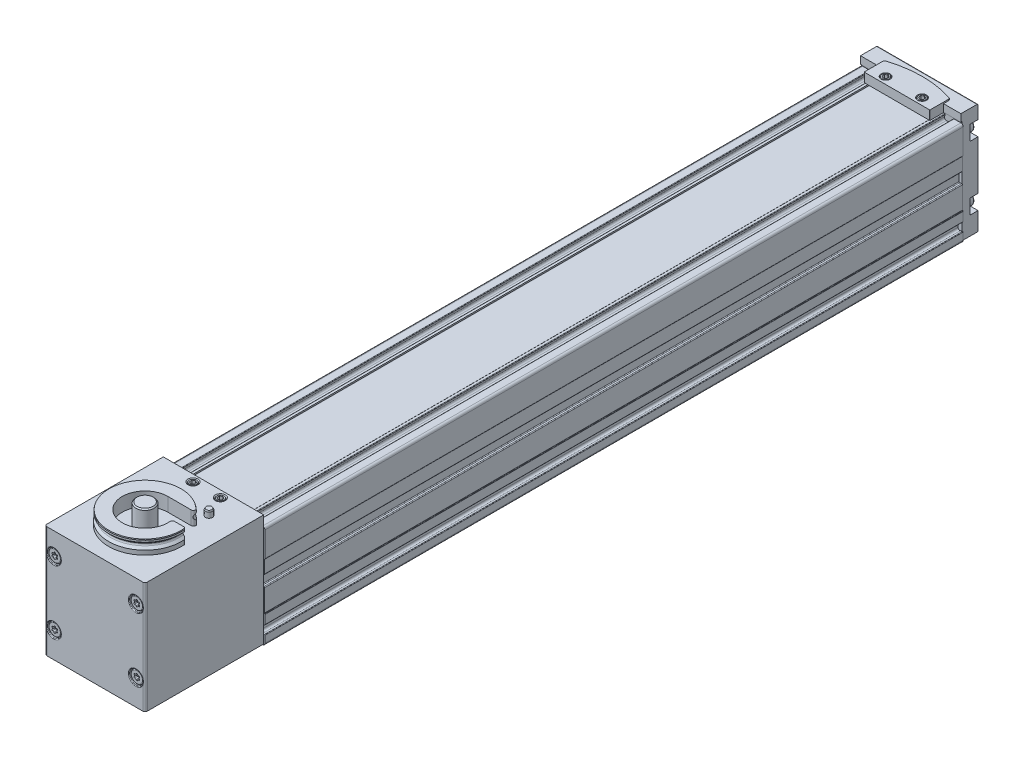
SolidWorks part; units mm, degrees
ref_plane "Front Plane" through (0, 0, 0) normal (0, 0, 1) x (1, 0, 0)
ref_plane "Top Plane" through (0, 0, 0) normal (0, 1, 0) x (1, 0, 0)
ref_plane "Right Plane" through (0, 0, 0) normal (1, 0, 0) x (0, 0, -1)
sketch "Sketch1" plane through (0, 0, 0) normal (0, 1, 0) x (1, 0, 0)
  line L0 (-21, -52) -> (21, -52)
  line L1 (22, -51) -> (22, 0)
  line L2 (22, 0) -> (-22, 0)
  line L3 (-22, 0) -> (-22, -51)
  arc A0 (-22, -51) -> (-21, -52) centre (-21, -51) ccw
  arc A1 (21, -52) -> (22, -51) centre (21, -51) ccw
extrude "Boss-Extrude1" add sketch "Sketch1" along normal blind 49
sketch "Sketch2" plane through (0, 0, 0) normal (0, 0, 1) x (1, 0, 0)
  line L0 (-22.5, -0.5) -> (22.5, -0.5)
  line L1 (22.5, -0.5) -> (22.5, 44.5)
  line L2 (22.5, 44.5) -> (13.4, 44.5)
  line L3 (13.4, 44.5) -> (13.4, 43.9)
  line L4 (13.4, 43.9) -> (-13.4, 43.9)
  line L5 (-13.4, 43.9) -> (-13.4, 44.5)
  line L6 (-13.4, 44.5) -> (-22.5, 44.5)
  line L7 (-22.5, 44.5) -> (-22.5, -0.5)
extrude "Boss-Extrude2" add sketch "Sketch2" against normal blind 306
sketch "Sketch3" plane through (0, 0, 0) normal (0, 0, 1) x (1, 0, 0)
  line L0 (-32.5, -5.5) -> (32.5, -5.5)
  line L1 (32.5, -5.5) -> (32.5, 49.5)
  line L2 (32.5, 49.5) -> (-32.5, 49.5)
  line L3 (-32.5, 49.5) -> (-32.5, -5.5)
  line L4 (-21.5, -0.5) -> (-18.4606, -0.5)
  line L5 (-18.2675, -0.2482) -> (-18.5464, 0.7929)
  line L6 (-17.7737, 1.8) -> (-15.1263, 1.8)
  line L7 (-14.3536, 0.7929) -> (-14.6325, -0.2482)
  line L8 (-14.4394, -0.5) -> (-7.5828, -0.5)
  line L9 (-7.4414, -0.4414) -> (-7.3086, -0.3086)
  line L10 (-7.1672, -0.25) -> (-4.8328, -0.25)
  line L11 (-4.6914, -0.3086) -> (-4.5586, -0.4414)
  line L12 (-4.4172, -0.5) -> (4.4172, -0.5)
  line L13 (4.5586, -0.4414) -> (4.6914, -0.3086)
  line L14 (4.8328, -0.25) -> (7.1672, -0.25)
  line L15 (7.3086, -0.3086) -> (7.4414, -0.4414)
  line L16 (7.5828, -0.5) -> (14.4394, -0.5)
  line L17 (14.6325, -0.2482) -> (14.3536, 0.7929)
  line L18 (15.1263, 1.8) -> (17.7737, 1.8)
  line L19 (18.5464, 0.7929) -> (18.2675, -0.2482)
  line L20 (18.4606, -0.5) -> (21.5, -0.5)
  line L21 (22.5, 0.5) -> (22.5, 3.5394)
  line L22 (22.2482, 3.7325) -> (21.2071, 3.4536)
  line L23 (20.2, 4.2263) -> (20.2, 6.8737)
  line L24 (21.2071, 7.6464) -> (22.2482, 7.3675)
  line L25 (22.5, 7.5606) -> (22.5, 11.4172)
  line L26 (22.4414, 11.5586) -> (22.3086, 11.6914)
  line L27 (22.25, 11.8328) -> (22.25, 21.3925)
  line L28 (21.8979, 21.6879) -> (21.0021, 21.53)
  line L29 (20.65, 21.8254) -> (20.65, 26.1746)
  line L30 (21.0021, 26.47) -> (21.8979, 26.3121)
  line L31 (22.25, 26.6075) -> (22.25, 32.1672)
  line L32 (22.3086, 32.3086) -> (22.4414, 32.4414)
  line L33 (22.5, 32.5828) -> (22.5, 43.5)
  line L34 (21.5, 44.5) -> (18.4606, 44.5)
  line L35 (18.2675, 44.2482) -> (18.5464, 43.2071)
  line L36 (17.7737, 42.2) -> (15.1263, 42.2)
  line L37 (14.3536, 43.2071) -> (14.6325, 44.2482)
  line L38 (14.4394, 44.5) -> (-14.4394, 44.5)
  line L39 (-14.6325, 44.2482) -> (-14.3536, 43.2071)
  line L40 (-15.1263, 42.2) -> (-17.7737, 42.2)
  line L41 (-18.5464, 43.2071) -> (-18.2675, 44.2482)
  line L42 (-18.4606, 44.5) -> (-21.5, 44.5)
  line L43 (-22.5, 43.5) -> (-22.5, 32.5828)
  line L44 (-22.4414, 32.4414) -> (-22.3086, 32.3086)
  line L45 (-22.25, 32.1672) -> (-22.25, 26.6075)
  line L46 (-21.8979, 26.3121) -> (-21.0021, 26.47)
  line L47 (-20.65, 26.1746) -> (-20.65, 21.8254)
  line L48 (-21.0021, 21.53) -> (-21.8979, 21.6879)
  line L49 (-22.25, 21.3925) -> (-22.25, 11.8328)
  line L50 (-22.3086, 11.6914) -> (-22.4414, 11.5586)
  line L51 (-22.5, 11.4172) -> (-22.5, 7.5606)
  line L52 (-22.2482, 7.3675) -> (-21.2071, 7.6464)
  line L53 (-20.2, 6.8737) -> (-20.2, 4.2263)
  line L54 (-21.2071, 3.4536) -> (-22.2482, 3.7325)
  line L55 (-22.5, 3.5394) -> (-22.5, 0.5)
  arc A0 (-22.5, 0.5) -> (-21.5, -0.5) centre (-21.5, 0.5) ccw
  arc A1 (-18.4606, -0.5) -> (-18.2675, -0.2482) centre (-18.4606, -0.3) ccw
  arc A2 (-18.5464, 0.7929) -> (-17.7737, 1.8) centre (-17.7737, 1) cw
  arc A3 (-15.1263, 1.8) -> (-14.3536, 0.7929) centre (-15.1263, 1) cw
  arc A4 (-14.6325, -0.2482) -> (-14.4394, -0.5) centre (-14.4394, -0.3) ccw
  arc A5 (-7.5828, -0.5) -> (-7.4414, -0.4414) centre (-7.5828, -0.3) ccw
  arc A6 (-7.3086, -0.3086) -> (-7.1672, -0.25) centre (-7.1672, -0.45) cw
  arc A7 (-4.8328, -0.25) -> (-4.6914, -0.3086) centre (-4.8328, -0.45) cw
  arc A8 (-4.5586, -0.4414) -> (-4.4172, -0.5) centre (-4.4172, -0.3) ccw
  arc A9 (4.4172, -0.5) -> (4.5586, -0.4414) centre (4.4172, -0.3) ccw
  arc A10 (4.6914, -0.3086) -> (4.8328, -0.25) centre (4.8328, -0.45) cw
  arc A11 (7.1672, -0.25) -> (7.3086, -0.3086) centre (7.1672, -0.45) cw
  arc A12 (7.4414, -0.4414) -> (7.5828, -0.5) centre (7.5828, -0.3) ccw
  arc A13 (14.4394, -0.5) -> (14.6325, -0.2482) centre (14.4394, -0.3) ccw
  arc A14 (14.3536, 0.7929) -> (15.1263, 1.8) centre (15.1263, 1) cw
  arc A15 (17.7737, 1.8) -> (18.5464, 0.7929) centre (17.7737, 1) cw
  arc A16 (18.2675, -0.2482) -> (18.4606, -0.5) centre (18.4606, -0.3) ccw
  arc A17 (21.5, -0.5) -> (22.5, 0.5) centre (21.5, 0.5) ccw
  arc A18 (22.5, 3.5394) -> (22.2482, 3.7325) centre (22.3, 3.5394) ccw
  arc A19 (21.2071, 3.4536) -> (20.2, 4.2263) centre (21, 4.2263) cw
  arc A20 (20.2, 6.8737) -> (21.2071, 7.6464) centre (21, 6.8737) cw
  arc A21 (22.2482, 7.3675) -> (22.5, 7.5606) centre (22.3, 7.5606) ccw
  arc A22 (22.5, 11.4172) -> (22.4414, 11.5586) centre (22.3, 11.4172) ccw
  arc A23 (22.3086, 11.6914) -> (22.25, 11.8328) centre (22.45, 11.8328) cw
  arc A24 (22.25, 21.3925) -> (21.8979, 21.6879) centre (21.95, 21.3925) ccw
  arc A25 (21.0021, 21.53) -> (20.65, 21.8254) centre (20.95, 21.8254) cw
  arc A26 (20.65, 26.1746) -> (21.0021, 26.47) centre (20.95, 26.1746) cw
  arc A27 (21.8979, 26.3121) -> (22.25, 26.6075) centre (21.95, 26.6075) ccw
  arc A28 (22.25, 32.1672) -> (22.3086, 32.3086) centre (22.45, 32.1672) cw
  arc A29 (22.4414, 32.4414) -> (22.5, 32.5828) centre (22.3, 32.5828) ccw
  arc A30 (22.5, 43.5) -> (21.5, 44.5) centre (21.5, 43.5) ccw
  arc A31 (18.4606, 44.5) -> (18.2675, 44.2482) centre (18.4606, 44.3) ccw
  arc A32 (18.5464, 43.2071) -> (17.7737, 42.2) centre (17.7737, 43) cw
  arc A33 (15.1263, 42.2) -> (14.3536, 43.2071) centre (15.1263, 43) cw
  arc A34 (14.6325, 44.2482) -> (14.4394, 44.5) centre (14.4394, 44.3) ccw
  arc A35 (-14.4394, 44.5) -> (-14.6325, 44.2482) centre (-14.4394, 44.3) ccw
  arc A36 (-14.3536, 43.2071) -> (-15.1263, 42.2) centre (-15.1263, 43) cw
  arc A37 (-17.7737, 42.2) -> (-18.5464, 43.2071) centre (-17.7737, 43) cw
  arc A38 (-18.2675, 44.2482) -> (-18.4606, 44.5) centre (-18.4606, 44.3) ccw
  arc A39 (-21.5, 44.5) -> (-22.5, 43.5) centre (-21.5, 43.5) ccw
  arc A40 (-22.5, 32.5828) -> (-22.4414, 32.4414) centre (-22.3, 32.5828) ccw
  arc A41 (-22.3086, 32.3086) -> (-22.25, 32.1672) centre (-22.45, 32.1672) cw
  arc A42 (-22.25, 26.6075) -> (-21.8979, 26.3121) centre (-21.95, 26.6075) ccw
  arc A43 (-21.0021, 26.47) -> (-20.65, 26.1746) centre (-20.95, 26.1746) cw
  arc A44 (-20.65, 21.8254) -> (-21.0021, 21.53) centre (-20.95, 21.8254) cw
  arc A45 (-21.8979, 21.6879) -> (-22.25, 21.3925) centre (-21.95, 21.3925) ccw
  arc A46 (-22.25, 11.8328) -> (-22.3086, 11.6914) centre (-22.45, 11.8328) cw
  arc A47 (-22.4414, 11.5586) -> (-22.5, 11.4172) centre (-22.3, 11.4172) ccw
  arc A48 (-22.5, 7.5606) -> (-22.2482, 7.3675) centre (-22.3, 7.5606) ccw
  arc A49 (-21.2071, 7.6464) -> (-20.2, 6.8737) centre (-21, 6.8737) cw
  arc A50 (-20.2, 4.2263) -> (-21.2071, 3.4536) centre (-21, 4.2263) cw
  arc A51 (-22.2482, 3.7325) -> (-22.5, 3.5394) centre (-22.3, 3.5394) ccw
extrude "Cut-Extrude1" cut sketch "Sketch3" against normal blind 306
ref_plane "Plane1" through (0, 0, -153) normal (0, 0, 1) x (1, 0, 0)
ref_plane "Plane2" through (0, 0, -271.25) normal (0, 0, 1) x (1, 0, 0)
sketch "Sketch4" plane through (0, 0, -271.25) normal (0, 0, 1) x (1, 0, 0)
  line L0 (-32.5, -5.5) -> (32.5, -5.5)
  line L1 (32.5, -5.5) -> (32.5, 49.5)
  line L2 (32.5, 49.5) -> (-32.5, 49.5)
  line L3 (-32.5, 49.5) -> (-32.5, -5.5)
  line L4 (-22.5, -0.5) -> (22.5, -0.5)
  line L5 (22.5, -0.5) -> (22.5, 44.5)
  line L6 (22.5, 44.5) -> (13.4, 44.5)
  line L7 (13.4, 44.5) -> (13.4, 43.9)
  line L8 (13.4, 43.9) -> (10, 43.9)
  line L9 (10, 43.9) -> (10, 28)
  line L10 (10, 28) -> (17, 28)
  line L11 (17, 28) -> (17, 21.5)
  line L12 (17, 21.5) -> (-17, 21.5)
  line L13 (-17, 21.5) -> (-17, 28)
  line L14 (-17, 28) -> (-10, 28)
  line L15 (-10, 28) -> (-10, 43.9)
  line L16 (-10, 43.9) -> (-13.4, 43.9)
  line L17 (-13.4, 43.9) -> (-13.4, 44.5)
  line L18 (-13.4, 44.5) -> (-22.5, 44.5)
  line L19 (-22.5, 44.5) -> (-22.5, -0.5)
extrude "Cut-Extrude2" cut sketch "Sketch4" along normal blind 266.5
sketch "Sketch5" plane through (0, 0, 0) normal (0, 0, 1) x (1, 0, 0)
  line L0 (-13, 44.06) -> (13, 44.06)
  line L1 (13, 44.06) -> (13, 44.16)
  line L2 (13, 44.16) -> (-13, 44.16)
  line L3 (-13, 44.16) -> (-13, 44.06)
extrude "Boss-Extrude3" add sketch "Sketch5" against normal blind 306
ref_plane "Plane3" through (0, 49, 0) normal (0, 1, 0) x (1, 0, 0)
sketch "Sketch6" plane through (0, 49, 0) normal (0, 1, 0) x (1, 0, 0)
  line L0 (14.9666, -28) -> (10.9545, -28)
  line L1 (0, -20) -> (10.198, -20)
  arc A0 (10.8779, -18.2667) -> (15.9644, -28.9333) centre (0, -30) ccw
  arc A1 (15.9644, -28.9333) -> (14.9666, -28) centre (14.9666, -29) ccw
  arc A2 (10.9545, -28) -> (9.9586, -29.0909) centre (10.9545, -29) ccw
  arc A3 (9.9586, -29.0909) -> (0, -20) centre (0, -30) cw
  arc A4 (10.198, -20) -> (10.8779, -18.2667) centre (10.198, -19) ccw
extrude "Boss-Extrude4" add sketch "Sketch6" along normal blind 6
sketch "Sketch7" plane through (0, 0, 0) normal (1, 0, 0) x (0, 0, -1)
  line L0 (-14.9737, 51.8697) -> (-14, 50.8959)
  line L1 (-14, 50.8959) -> (-14, 49)
  line L2 (-14, 49) -> (-4, 49)
  line L3 (-4, 49) -> (-4, 55)
  line L4 (-4, 55) -> (-14.2072, 55)
  line L5 (-14.2072, 55) -> (-14.1, 54.6)
  line L6 (-14.1, 54.6) -> (-14.1, 53.8041)
  line L7 (-14.1, 53.8041) -> (-14.9737, 52.9303)
  line L8 (-30, 49) -> (-30, 55) construction
  arc A0 (-14.9737, 52.9303) -> (-14.9737, 51.8697) centre (-14.4434, 52.4) ccw
revolve "Cut-Revolve1" cut sketch "Sketch7" angle 360 about L8 reverse direction yes
ref_plane "Plane4" through (0, 0, 30) normal (0, 0, 1) x (1, 0, 0)
sketch "Sketch8" plane through (0, 0, 30) normal (0, 0, 1) x (1, 0, 0)
  line L0 (0, 58) -> (3.5, 58)
  line L1 (3.5, 58) -> (4, 57.5)
  line L2 (4, 57.5) -> (4, 49)
  line L3 (4, 49) -> (0, 49)
  line L4 (0, 49) -> (0, 58)
  line L5 (0, 49) -> (0, 58) construction
revolve "Revolve1" add sketch "Sketch8" angle 360 about L5 reverse direction yes
ref_plane "Plane5" through (0, 68.9, 0) normal (0, 1, 0) x (1, 0, 0)
ref_plane "Plane6" through (0, 52.6, 0) normal (0, 1, 0) x (1, 0, 0)
ref_plane "Plane7" through (-18, 0, 0) normal (1, 0, 0) x (0, 0, -1)
sketch "Sketch9" plane through (-18, 0, 0) normal (1, 0, 0) x (0, 0, -1)
  line L0 (-52, 39.25) -> (-52, 42.6)
  line L1 (-51.7, 42.3) -> (-48.8, 42.3)
  line L2 (-48.8, 42.3) -> (-48.8, 42)
  line L3 (-48.8, 42) -> (-51.3, 42)
  line L4 (-51.6, 41.7) -> (-51.6, 39.25)
  line L5 (-51.6, 39.25) -> (-52, 39.25)
  line L6 (-51.6, 39.25) -> (-52, 39.25) construction
  arc A0 (-52, 42.6) -> (-51.7, 42.3) centre (-51.7, 42.6) ccw
  arc A1 (-51.3, 42) -> (-51.6, 41.7) centre (-51.3, 41.7) ccw
revolve "Cut-Revolve2" cut sketch "Sketch9" angle 360 about L6 reverse direction yes
sketch "Sketch10" plane through (-18, 0, 0) normal (1, 0, 0) x (0, 0, -1)
  line L0 (-52, 39.25) -> (-52, 11.25)
pattern_linear "LPattern1" count 2 spacing 28 along (0, -1, 0) of "Cut-Revolve2"
ref_plane "Plane8" through (18, 0, 0) normal (1, 0, 0) x (0, 0, -1)
sketch "Sketch11" plane through (18, 0, 0) normal (1, 0, 0) x (0, 0, -1)
  line L0 (-52, 39.25) -> (-52, 42.6)
  line L1 (-51.7, 42.3) -> (-48.8, 42.3)
  line L2 (-48.8, 42.3) -> (-48.8, 42)
  line L3 (-48.8, 42) -> (-51.3, 42)
  line L4 (-51.6, 41.7) -> (-51.6, 39.25)
  line L5 (-51.6, 39.25) -> (-52, 39.25)
  line L6 (-51.6, 39.25) -> (-52, 39.25) construction
  arc A0 (-52, 42.6) -> (-51.7, 42.3) centre (-51.7, 42.6) ccw
  arc A1 (-51.3, 42) -> (-51.6, 41.7) centre (-51.3, 41.7) ccw
revolve "Cut-Revolve3" cut sketch "Sketch11" angle 360 about L6 reverse direction yes
sketch "Sketch12" plane through (18, 0, 0) normal (1, 0, 0) x (0, 0, -1)
  line L0 (-52, 39.25) -> (-52, 11.25)
pattern_linear "LPattern2" count 2 spacing 28 along (0, -1, 0) of "Cut-Revolve3"
ref_plane "Plane9" through (0, 0, 52) normal (0, 0, 1) x (1, 0, 0)
sketch "Sketch13" plane through (0, 0, 52) normal (0, 0, 1) x (1, 0, 0)
  arc A0 (-19.1621, 38.8936) -> (-18.8897, 38.4218) centre (-18.9699, 38.69) ccw
  arc A1 (-18.8897, 38.4218) -> (-18.2724, 38.0654) centre (-18.7492, 37.9523) cw
  arc A2 (-18.2724, 38.0654) -> (-17.7276, 38.0654) centre (-18, 38.13) ccw
  arc A3 (-17.7276, 38.0654) -> (-17.1103, 38.4218) centre (-17.2508, 37.9523) cw
  arc A4 (-17.1103, 38.4218) -> (-16.8379, 38.8936) centre (-17.0301, 38.69) ccw
  arc A5 (-16.8379, 38.8936) -> (-16.8379, 39.6064) centre (-16.5016, 39.25) cw
  arc A6 (-16.8379, 39.6064) -> (-17.1103, 40.0782) centre (-17.0301, 39.81) ccw
  arc A7 (-17.1103, 40.0782) -> (-17.7276, 40.4346) centre (-17.2508, 40.5477) cw
  arc A8 (-17.7276, 40.4346) -> (-18.2724, 40.4346) centre (-18, 40.37) ccw
  arc A9 (-18.2724, 40.4346) -> (-18.8897, 40.0782) centre (-18.7492, 40.5477) cw
  arc A10 (-18.8897, 40.0782) -> (-19.1621, 39.6064) centre (-18.9699, 39.81) ccw
  arc A11 (-19.1621, 39.6064) -> (-19.1621, 38.8936) centre (-19.4984, 39.25) cw
extrude "Cut-Extrude3" cut sketch "Sketch13" against normal blind 1.67
sketch "Sketch14" plane through (0, 0, 52) normal (0, 0, 1) x (1, 0, 0)
  line L0 (-18, 39.25) -> (18, 39.25)
  line L1 (-18, 39.25) -> (-18, 11.25)
pattern_linear "LPattern3" count 2 spacing 36 along (1, 0, 0) count 2 spacing 28 along (0, -1, 0) of "Cut-Extrude3"
sketch "Sketch15" plane through (0, 0, 0) normal (1, 0, 0) x (0, 0, -1)
  line L0 (305.5, 45.25) -> (306, 45.25)
  line L1 (306, 45.25) -> (306, 0)
  line L2 (306, 0) -> (312.55, 0)
  line L3 (313, 0.45) -> (313, 48.05)
  line L4 (312.55, 48.5) -> (305.5, 48.5)
  line L5 (305.5, 48.5) -> (305.5, 45.25)
  arc A0 (312.55, 0) -> (313, 0.45) centre (312.55, 0.45) ccw
  arc A1 (313, 48.05) -> (312.55, 48.5) centre (312.55, 48.05) ccw
extrude "Boss-Extrude5" add sketch "Sketch15" against normal blind 22 and the other way blind 22
ref_plane "Plane10" through (0, 49.1, 0) normal (0, 1, 0) x (1, 0, 0)
sketch "Sketch16" plane through (0, 49.1, 0) normal (0, 1, 0) x (1, 0, 0)
  line L0 (-14.2, 299.5) -> (14.2, 299.5)
  line L1 (14.4, 299.7) -> (14.4, 307.692)
  line L2 (-14.4, 307.692) -> (-14.4, 299.7)
  arc A0 (-14.4, 299.7) -> (-14.2, 299.5) centre (-14.2, 299.7) ccw
  arc A1 (14.2, 299.5) -> (14.4, 299.7) centre (14.2, 299.7) ccw
  arc A2 (14.4, 307.692) -> (13.8814, 308.4055) centre (13.65, 307.692) ccw
  arc A3 (13.8814, 308.4055) -> (-13.8814, 308.4055) centre (0, 265.6) ccw
  arc A4 (-13.8814, 308.4055) -> (-14.4, 307.692) centre (-13.65, 307.692) ccw
extrude "Boss-Extrude6" add sketch "Sketch16" against normal blind 4
ref_plane "Plane11" through (0, 0, -313) normal (0, 0, 1) x (1, 0, 0)
sketch "Sketch17" plane through (0, 0, -313) normal (0, 0, 1) x (1, 0, 0)
  line L0 (18, 36) -> (22, 36)
  line L1 (22, 36) -> (22, 42.5)
  line L2 (22, 42.5) -> (18, 42.5)
  arc A0 (18, 42.5) -> (18, 36) centre (18, 39.25) ccw
extrude "Cut-Extrude4" cut sketch "Sketch17" along normal blind 3.4
sketch "Sketch18" plane through (0, 0, -313) normal (0, 0, 1) x (1, 0, 0)
  line L0 (18, 39.25) -> (18, 11.25)
pattern_linear "LPattern4" count 2 spacing 28 along (0, -1, 0) of "Cut-Extrude4"
sketch "Sketch19" plane through (0, 0, -313) normal (0, 0, 1) x (1, 0, 0)
  line L0 (-22, 36) -> (-18, 36)
  line L1 (-18, 42.5) -> (-22, 42.5)
  line L2 (-22, 42.5) -> (-22, 36)
  arc A0 (-18, 36) -> (-18, 42.5) centre (-18, 39.25) ccw
extrude "Cut-Extrude5" cut sketch "Sketch19" along normal blind 3.4
sketch "Sketch20" plane through (0, 0, -313) normal (0, 0, 1) x (1, 0, 0)
  line L0 (-18, 39.25) -> (-18, 11.25)
pattern_linear "LPattern5" count 2 spacing 28 along (0, -1, 0) of "Cut-Extrude5"
sketch "Sketch21" plane through (18, 0, 0) normal (1, 0, 0) x (0, 0, -1)
  line L0 (309.6, 39.25) -> (309.6, 42)
  line L1 (309.6, 42) -> (312.3, 42)
  line L2 (312.6, 41.7) -> (312.6, 39.25)
  line L3 (312.6, 39.25) -> (309.6, 39.25)
  line L4 (312.6, 39.25) -> (309.6, 39.25) construction
  arc A0 (312.3, 42) -> (312.6, 41.7) centre (312.3, 41.7) cw
revolve "Revolve2" add sketch "Sketch21" angle 360 about L4 reverse direction yes
sketch "Sketch22" plane through (18, 0, 0) normal (1, 0, 0) x (0, 0, -1)
  line L0 (309.6, 39.25) -> (309.6, 11.25)
pattern_linear "LPattern6" count 2 spacing 28 along (0, -1, 0) of "Revolve2"
sketch "Sketch23" plane through (-18, 0, 0) normal (1, 0, 0) x (0, 0, -1)
  line L0 (309.6, 39.25) -> (309.6, 42)
  line L1 (309.6, 42) -> (312.3, 42)
  line L2 (312.6, 41.7) -> (312.6, 39.25)
  line L3 (312.6, 39.25) -> (309.6, 39.25)
  line L4 (312.6, 39.25) -> (309.6, 39.25) construction
  arc A0 (312.3, 42) -> (312.6, 41.7) centre (312.3, 41.7) cw
revolve "Revolve3" add sketch "Sketch23" angle 360 about L4 reverse direction yes
sketch "Sketch24" plane through (-18, 0, 0) normal (1, 0, 0) x (0, 0, -1)
  line L0 (309.6, 39.25) -> (309.6, 11.25)
pattern_linear "LPattern7" count 2 spacing 28 along (0, -1, 0) of "Revolve3"
sketch "Sketch25" plane through (0, 0, -313) normal (0, 0, 1) x (1, 0, 0)
  arc A0 (-19.1621, 38.8936) -> (-18.8897, 38.4218) centre (-18.9699, 38.69) ccw
  arc A1 (-18.8897, 38.4218) -> (-18.2724, 38.0654) centre (-18.7492, 37.9523) cw
  arc A2 (-18.2724, 38.0654) -> (-17.7276, 38.0654) centre (-18, 38.13) ccw
  arc A3 (-17.7276, 38.0654) -> (-17.1103, 38.4218) centre (-17.2508, 37.9523) cw
  arc A4 (-17.1103, 38.4218) -> (-16.8379, 38.8936) centre (-17.0301, 38.69) ccw
  arc A5 (-16.8379, 38.8936) -> (-16.8379, 39.6064) centre (-16.5016, 39.25) cw
  arc A6 (-16.8379, 39.6064) -> (-17.1103, 40.0782) centre (-17.0301, 39.81) ccw
  arc A7 (-17.1103, 40.0782) -> (-17.7276, 40.4346) centre (-17.2508, 40.5477) cw
  arc A8 (-17.7276, 40.4346) -> (-18.2724, 40.4346) centre (-18, 40.37) ccw
  arc A9 (-18.2724, 40.4346) -> (-18.8897, 40.0782) centre (-18.7492, 40.5477) cw
  arc A10 (-18.8897, 40.0782) -> (-19.1621, 39.6064) centre (-18.9699, 39.81) ccw
  arc A11 (-19.1621, 39.6064) -> (-19.1621, 38.8936) centre (-19.4984, 39.25) cw
extrude "Cut-Extrude6" cut sketch "Sketch25" along normal blind 1.67
sketch "Sketch26" plane through (0, 0, -313) normal (0, 0, 1) x (1, 0, 0)
  line L0 (-18, 39.25) -> (18, 39.25)
  line L1 (-18, 39.25) -> (-18, 11.25)
pattern_linear "LPattern8" count 2 spacing 36 along (1, 0, 0) count 2 spacing 28 along (0, -1, 0) of "Cut-Extrude6"
sketch "Sketch27" plane through (0, 0, 0) normal (1, 0, 0) x (0, 0, -1)
  line L0 (312.6, 31.5) -> (312.6, 35.25)
  line L1 (312.1, 35.75) -> (307.6, 35.75)
  line L2 (307.6, 35.75) -> (307.6, 36.5)
  line L3 (307.6, 36.5) -> (313, 36.5)
  line L4 (313, 36.5) -> (313, 31.5)
  line L5 (313, 31.5) -> (312.6, 31.5)
  line L6 (313, 31.5) -> (312.6, 31.5) construction
  arc A0 (312.6, 35.25) -> (312.1, 35.75) centre (312.1, 35.25) ccw
revolve "Cut-Revolve4" cut sketch "Sketch27" angle 360 about L6 reverse direction yes
sketch "Sketch28" plane through (0, 0, -313) normal (0, 0, 1) x (1, 0, 0)
  arc A0 (-1.8667, 30.9276) -> (-1.4291, 30.1696) centre (-1.558, 30.6005) ccw
  arc A1 (-1.4291, 30.1696) -> (-0.4376, 29.5972) centre (-1.2034, 29.4156) cw
  arc A2 (-0.4376, 29.5972) -> (0.4376, 29.5972) centre (0, 29.701) ccw
  arc A3 (0.4376, 29.5972) -> (1.4291, 30.1696) centre (1.2034, 29.4156) cw
  arc A4 (1.4291, 30.1696) -> (1.8667, 30.9276) centre (1.558, 30.6005) ccw
  arc A5 (1.8667, 30.9276) -> (1.8667, 32.0724) centre (2.4069, 31.5) cw
  arc A6 (1.8667, 32.0724) -> (1.4291, 32.8304) centre (1.558, 32.3995) ccw
  arc A7 (1.4291, 32.8304) -> (0.4376, 33.4028) centre (1.2034, 33.5844) cw
  arc A8 (0.4376, 33.4028) -> (-0.4376, 33.4028) centre (0, 33.299) ccw
  arc A9 (-0.4376, 33.4028) -> (-1.4291, 32.8304) centre (-1.2034, 33.5844) cw
  arc A10 (-1.4291, 32.8304) -> (-1.8667, 32.0724) centre (-1.558, 32.3995) ccw
  arc A11 (-1.8667, 32.0724) -> (-1.8667, 30.9276) centre (-2.4069, 31.5) cw
extrude "Cut-Extrude7" cut sketch "Sketch28" along normal blind 2.43
sketch "Sketch29" plane through (0, 0, 0) normal (1, 0, 0) x (0, 0, -1)
  line L0 (313, 12) -> (313, 7.136)
  line L1 (313, 7.136) -> (312.419, 7.717)
  line L2 (312.419, 7.717) -> (304.1, 7.717)
  line L3 (304.1, 7.717) -> (304.1, 12)
  line L4 (304.1, 12) -> (313, 12)
  line L5 (304.1, 12) -> (313, 12) construction
revolve "Cut-Revolve5" cut sketch "Sketch29" angle 360 about L5 reverse direction yes
cosmetic thread "Cosmetic Thread1" parameters "D1"=8.9, "D2"=9.728
ref_plane "Plane12" through (0, 0, 3) normal (0, 0, 1) x (1, 0, 0)
sketch "Sketch30" plane through (0, 0, 3) normal (0, 0, 1) x (1, 0, 0)
  line L0 (6, 49) -> (8.2, 49)
  line L1 (8.2, 49) -> (7.75, 48.7)
  line L2 (7.75, 48.7) -> (7.57, 48.9)
  line L3 (7.57, 48.9) -> (6, 48.9)
  line L4 (6, 48.9) -> (6, 49)
  line L5 (6, 48.9) -> (6, 49) construction
revolve "Cut-Revolve6" cut sketch "Sketch30" angle 360 about L5 reverse direction yes
sketch "Sketch31" plane through (0, 0, 3) normal (0, 0, 1) x (1, 0, 0)
  line L0 (6, 49) -> (-6, 49)
pattern_linear "LPattern9" count 2 spacing 12 along (-1, 0, 0) of "Cut-Revolve6"
ref_plane "Plane13" through (0, 47.2, 0) normal (0, 1, 0) x (1, 0, 0)
sketch "Sketch32" plane through (0, 47.2, 0) normal (0, 1, 0) x (1, 0, 0)
  line L0 (5, -3.5774) -> (6, -4.1547)
  line L1 (6, -4.1547) -> (7, -3.5774)
  line L2 (7, -3.5774) -> (7, -2.4226)
  line L3 (7, -2.4226) -> (6, -1.8453)
  line L4 (6, -1.8453) -> (5, -2.4226)
  line L5 (5, -2.4226) -> (5, -3.5774)
extrude "Cut-Extrude8" cut sketch "Sketch32" along normal blind 2.1
sketch "Sketch33" plane through (0, 49, 0) normal (0, 1, 0) x (1, 0, 0)
  line L0 (6, -3) -> (-6, -3)
pattern_linear "LPattern10" count 2 spacing 12 along (-1, 0, 0) of "Cut-Extrude8"
ref_plane "Plane14" through (0, 0, -302.5) normal (0, 0, 1) x (1, 0, 0)
sketch "Sketch34" plane through (0, 0, -302.5) normal (0, 0, 1) x (1, 0, 0)
  line L0 (8, 49.1) -> (10, 49.1)
  line L1 (10, 49.1) -> (9.621, 48.721)
  line L2 (9.621, 48.721) -> (9.621, 45.1)
  line L3 (9.621, 45.1) -> (8, 45.1)
  line L4 (8, 45.1) -> (8, 49.1)
  line L5 (8, 45.1) -> (8, 49.1) construction
revolve "Cut-Revolve7" cut sketch "Sketch34" angle 360 about L5 reverse direction yes
cosmetic thread "Cosmetic Thread2" parameters "D1"=4, "D2"=4
sketch "Sketch35" plane through (0, 0, -302.5) normal (0, 0, 1) x (1, 0, 0)
  line L0 (8, 49.1) -> (-8, 49.1)
pattern_linear "LPattern11" count 2 spacing 16 along (-1, 0, 0) of "Cut-Revolve7"
cosmetic thread "Cosmetic Thread3" parameters "D1"=4, "D2"=4
sketch "Sketch36" plane through (0, 0, -302.5) normal (0, 0, 1) x (1, 0, 0)
  line L0 (8, 49.1) -> (9.5705, 49.1)
  line L1 (9.5705, 49.1) -> (10, 48.6705)
  line L2 (10, 48.6705) -> (10, 44.5)
  line L3 (10, 44.5) -> (9.6, 44.1)
  line L4 (9.6, 44.1) -> (8, 44.1)
  line L5 (8, 44.1) -> (8, 49.1)
  line L6 (8, 44.1) -> (8, 49.1) construction
revolve "Revolve4" add sketch "Sketch36" angle 360 about L6 reverse direction yes
sketch "Sketch37" plane through (0, 0, -302.5) normal (0, 0, 1) x (1, 0, 0)
  line L0 (8, 49.1) -> (-8, 49.1)
pattern_linear "LPattern12" count 2 spacing 16 along (-1, 0, 0) of "Revolve4"
sketch "Sketch38" plane through (0, 49, 0) normal (0, 1, 0) x (1, 0, 0)
  line L0 (7, 301.9226) -> (8, 301.3453)
  line L1 (8, 301.3453) -> (9, 301.9226)
  line L2 (9, 301.9226) -> (9, 303.0774)
  line L3 (9, 303.0774) -> (8, 303.6547)
  line L4 (8, 303.6547) -> (7, 303.0774)
  line L5 (7, 303.0774) -> (7, 301.9226)
extrude "Cut-Extrude9" cut sketch "Sketch38" along normal blind 2.84 and the other way blind 2.84
sketch "Sketch39" plane through (0, 49, 0) normal (0, 1, 0) x (1, 0, 0)
  line L0 (8, 302.5) -> (-8, 302.5)
pattern_linear "LPattern13" count 2 spacing 16 along (-1, 0, 0) of "Cut-Extrude9"
ref_plane "Plane15" through (4, 0, 0) normal (1, 0, 0) x (0, 0, -1)
sketch "Sketch40" plane through (4, 0, 0) normal (1, 0, 0) x (0, 0, -1)
  line L0 (-46, 1) -> (-42.9, 1)
  line L1 (-42.5, 1.4) -> (-42.5, 5)
  line L2 (-42.5, 5) -> (-41.95, 5)
  line L3 (-41.95, 5) -> (-41.95, 0.3)
  line L4 (-41.65, 0) -> (-46, 0)
  line L5 (-46, 0) -> (-46, 1)
  line L6 (-46, 0) -> (-46, 1) construction
  arc A0 (-42.9, 1) -> (-42.5, 1.4) centre (-42.9, 1.4) ccw
  arc A1 (-41.95, 0.3) -> (-41.65, 0) centre (-41.65, 0.3) ccw
revolve "Cut-Revolve8" cut sketch "Sketch40" angle 360 about L6 reverse direction yes
ref_plane "Plane16" through (-4, 0, 0) normal (1, 0, 0) x (0, 0, -1)
sketch "Sketch41" plane through (-4, 0, 0) normal (1, 0, 0) x (0, 0, -1)
  line L0 (-14, 1) -> (-10.9, 1)
  line L1 (-10.5, 1.4) -> (-10.5, 5)
  line L2 (-10.5, 5) -> (-9.95, 5)
  line L3 (-9.95, 5) -> (-9.95, 0.3)
  line L4 (-9.65, 0) -> (-14, 0)
  line L5 (-14, 0) -> (-14, 1)
  line L6 (-14, 0) -> (-14, 1) construction
  arc A0 (-10.9, 1) -> (-10.5, 1.4) centre (-10.9, 1.4) ccw
  arc A1 (-9.95, 0.3) -> (-9.65, 0) centre (-9.65, 0.3) ccw
revolve "Cut-Revolve9" cut sketch "Sketch41" angle 360 about L6 reverse direction yes
sketch "Sketch42" plane through (0, 0, 0) normal (0, 1, 0) x (1, 0, 0)
  arc A0 (2.3585, -46.5034) -> (2.7433, -47.1699) centre (2.6299, -46.791) ccw
  arc A1 (2.7433, -47.1699) -> (3.6152, -47.6733) centre (2.9417, -47.833) cw
  arc A2 (3.6152, -47.6733) -> (4.3848, -47.6733) centre (4, -47.582) ccw
  arc A3 (4.3848, -47.6733) -> (5.2567, -47.1699) centre (5.0583, -47.833) cw
  arc A4 (5.2567, -47.1699) -> (5.6415, -46.5034) centre (5.3701, -46.791) ccw
  arc A5 (5.6415, -46.5034) -> (5.6415, -45.4966) centre (6.1165, -46) cw
  arc A6 (5.6415, -45.4966) -> (5.2567, -44.8301) centre (5.3701, -45.209) ccw
  arc A7 (5.2567, -44.8301) -> (4.3848, -44.3267) centre (5.0583, -44.167) cw
  arc A8 (4.3848, -44.3267) -> (3.6152, -44.3267) centre (4, -44.418) ccw
  arc A9 (3.6152, -44.3267) -> (2.7433, -44.8301) centre (2.9417, -44.167) cw
  arc A10 (2.7433, -44.8301) -> (2.3585, -45.4966) centre (2.6299, -45.209) ccw
  arc A11 (2.3585, -45.4966) -> (2.3585, -46.5034) centre (1.8835, -46) cw
extrude "Cut-Extrude10" cut sketch "Sketch42" along normal blind 2.5
sketch "Sketch43" plane through (0, 0, 0) normal (0, 1, 0) x (1, 0, 0)
  line L0 (4, -46) -> (-4, -14)
pattern_linear "LPattern14" count 2 spacing 32.9848 along (-0.2425, 0, -0.9701) of "Cut-Extrude10"
ref_plane "Plane17" through (12.9904, 0, 7.5) normal (0.866, 0, 0.5) x (0.5, 0, -0.866)
sketch "Sketch44" plane through (12.9904, 0, 7.5) normal (0.866, 0, 0.5) x (0.5, 0, -0.866)
  line L0 (-5.4808, 51.83) -> (-4.2694, 51.83)
  line L1 (-4.2694, 51.83) -> (-3.9808, 51.33)
  line L2 (-3.9808, 51.33) -> (-3.9808, 49)
  line L3 (-3.9808, 49) -> (-5.4808, 49)
  line L4 (-5.4808, 49) -> (-5.4808, 51.83)
  line L5 (-5.4808, 49) -> (-5.4808, 51.83) construction
revolve "Revolve5" add sketch "Sketch44" angle 360 about L5 reverse direction yes
ref_plane "Plane18" through (0, -0.5, 0) normal (0, 1, 0) x (1, 0, 0)
ref_plane "Plane19" through (0, 0, -38) normal (0, 0, 1) x (1, 0, 0)
ref_plane "Plane20" through (0, 49, 0) normal (0, 1, 0) x (1, 0, 0)
ref_plane "ANBAU XY" through (0, -0.5, 0) normal (0, -1, 0) x (-1, 0, 0)
ref_plane "ANBAU XZ" through (0, 0, 0) normal (0, 0, -1) x (-1, 0, 0)
ref_plane "ANBAU YZ" through (0, 0, 0) normal (1, 0, 0) x (0, 0, -1)
ref_axis "ANBAU X" through (-80.9, -0.5, 0) along (1, 0, 0)
ref_axis "ANBAU Y" through (0, -0.5, -50) along (0, 0, 1)
ref_axis "ANBAU Z" through (0, -50, 0) along (0, 1, 0)
sketch3d "ANBAU"
  point P0 (0, -0.5, 0)
ref_plane "CP_PLUG XY" through (0, 0, -313) normal (0, 0, -1) x (-1, 0, 0)
ref_plane "CP_PLUG XZ" through (0, 12, 0) normal (0, 1, 0) x (1, 0, 0)
ref_plane "CP_PLUG YZ" through (0, 0, 0) normal (1, 0, 0) x (0, 0, -1)
ref_axis "CP_PLUG X" through (-80.9, 12, -313) along (1, 0, 0)
ref_axis "CP_PLUG Y" through (0, 50, -313) along (0, -1, 0)
ref_axis "CP_PLUG Z" through (0, 12, -80.9) along (0, 0, 1)
sketch3d "CP_PLUG"
  point P0 (0, 12, -313)
ref_plane "HUB_CP XY" through (0, 49, 0) normal (0, 1, 0) x (1, 0, 0)
ref_plane "HUB_CP XZ" through (0, 0, 30) normal (0, 0, 1) x (1, 0, 0)
ref_plane "HUB_CP YZ" through (0, 0, 0) normal (1, 0, 0) x (0, 0, -1)
ref_axis "HUB_CP X" through (-80.9, 49, 30) along (1, 0, 0)
ref_axis "HUB_CP Y" through (0, 49, 50) along (0, 0, -1)
ref_axis "HUB_CP Z" through (0, 50, 30) along (0, -1, 0)
sketch3d "HUB_CP"
  point P0 (0, 49, 30)
ref_plane "MOUNT XY" through (0, 49, 0) normal (0, -1, 0) x (-1, 0, 0)
ref_plane "MOUNT XZ" through (0, 0, 30) normal (0, 0, -1) x (-1, 0, 0)
ref_plane "MOUNT YZ" through (0, 0, 0) normal (1, 0, 0) x (0, 0, -1)
ref_axis "MOUNT X" through (-80.9, 49, 30) along (1, 0, 0)
ref_axis "MOUNT Y" through (0, 49, -50) along (0, 0, 1)
ref_axis "MOUNT Z" through (0, -50, 30) along (0, 1, 0)
sketch3d "MOUNT"
  point P0 (0, 49, 30)
ref_plane "SLIDE1_CP XY" through (0, 0, -38) normal (0, 0, -1) x (-1, 0, 0)
ref_plane "SLIDE1_CP XZ" through (0, 21.5, 0) normal (0, 1, 0) x (1, 0, 0)
ref_plane "SLIDE1_CP YZ" through (0, 0, 0) normal (1, 0, 0) x (0, 0, -1)
ref_axis "SLIDE1_CP X" through (-80.9, 21.5, -38) along (1, 0, 0)
ref_axis "SLIDE1_CP Y" through (0, 50, -38) along (0, -1, 0)
ref_axis "SLIDE1_CP Z" through (0, 21.5, -80.9) along (0, 0, 1)
sketch3d "SLIDE1_CP"
  point P0 (0, 21.5, -38)
other "Freeze***"
